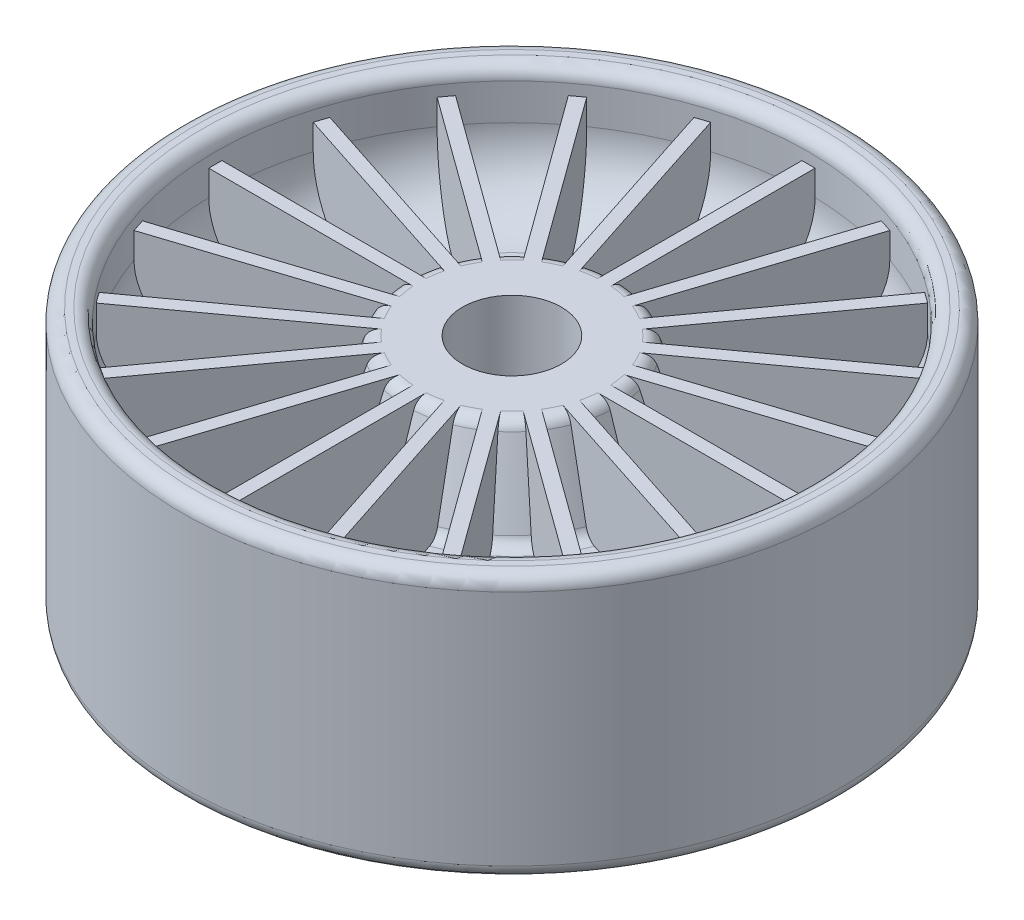
SolidWorks part; units mm, degrees
ref_plane "Front Plane" through (0, 0, 0) normal (0, 0, 1) x (1, 0, 0)
ref_plane "Top Plane" through (0, 0, 0) normal (0, 1, 0) x (1, 0, 0)
ref_plane "Right Plane" through (0, 0, 0) normal (1, 0, 0) x (0, 0, -1)
sketch "Sketch2" plane through (0, 0, 0) normal (0, 0, 1) x (1, 0, 0)
  line L0 (0, 0) -> (0, 39.9092) construction
  line L1 (0, 0) -> (-61.0599, 0) construction
  line L2 (-9.525, -20.764) -> (-9.525, 20.764)
  line L3 (-9.525, 20.764) -> (-19.685, 20.764)
  line L4 (-19.685, 20.764) -> (-25.4, 3.175)
  line L5 (-25.4, 3.175) -> (-57.15, 3.175)
  line L6 (-57.15, 3.175) -> (-57.15, 25.4)
  line L7 (-57.15, 25.4) -> (-63.5, 25.4)
  line L8 (-63.5, 25.4) -> (-63.5, -25.4)
  line L9 (-9.525, -20.764) -> (-19.685, -20.764)
  line L10 (-19.685, -20.764) -> (-25.4, -3.175)
  line L11 (-25.4, -3.175) -> (-57.15, -3.175)
  line L12 (-57.15, -3.175) -> (-57.15, -25.4)
  line L13 (-57.15, -25.4) -> (-63.5, -25.4)
  point P13 (-9.525, 0)
  point P19 (-63.5, 0)
  dimension "D1" = 19.05
  dimension "D2" = 10.16
  dimension "D3" = 18
  dimension "D4" = 6.35
  dimension "D5" = 50.8
  dimension "D6" = 6.35
  dimension "D7" = 50.8
  dimension "D8" = 127
revolve "Revolve2" add sketch "Sketch2" angle 360 about L0
fillet "Fillet1" radius 2.54 8 edges at (0, -20.764, -19.685) (0, -3.175, -25.4) (0, 20.764, -19.685) (0, 3.175, -25.4) (0, -25.4, -63.5) (0, 25.4, -57.15) (0, 25.4, -63.5) (0, -25.4, -57.15)
fillet "Fillet2" radius 12.7 2 edges at (0, -3.175, -57.15) (0, 3.175, -57.15)
sketch "Sketch4" plane through (0, 20.764, 0) normal (0, 1, 0) x (1, 0, 0)
  line L0 (0, 27.2454) -> (0, 44.45)
  circle A0 centre (0, 0) radius 27.2454 construction
  circle A1 centre (0, 0) radius 44.45 construction
rib "Rib1" sketch "Sketch4" sketch "Sketch4" thickness 2.54 extrusion direction normal to sketch draft on no parameters "D1"=2.54
mirror "Mirror1" about plane through (0, 0, 0) normal (0, 1, 0) of "Rib1"
pattern_circular "CirPattern1" count 20 over 360 about axis through (0, 0, 0) along (0, -1, 0) of "Rib1", "Mirror1"
